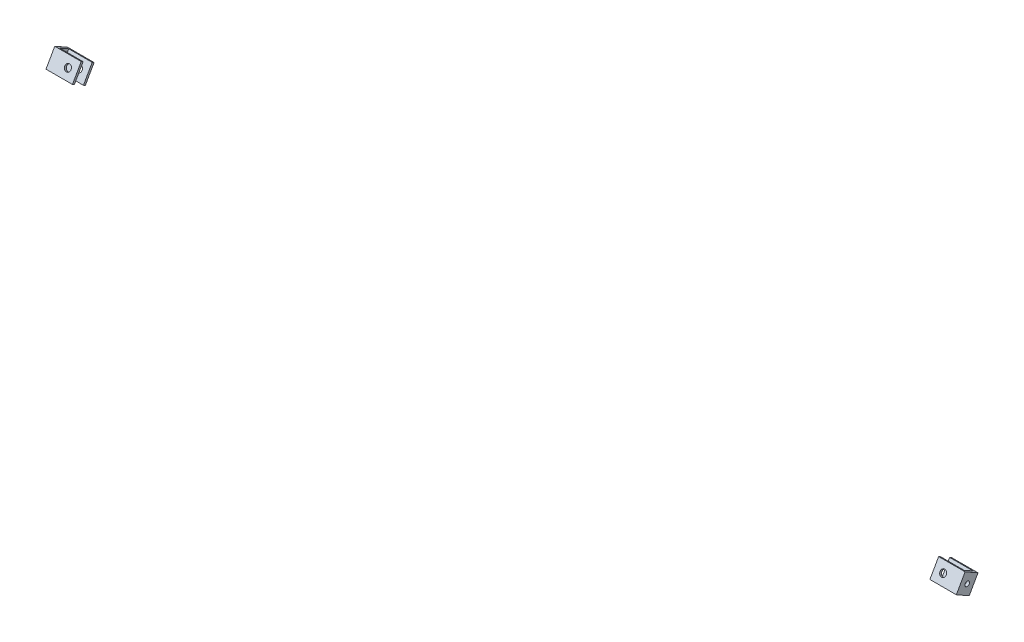
SolidWorks part; units mm, degrees
ref_plane "Front Plane" through (0, 0, 0) normal (0, 0, 1) x (1, 0, 0)
ref_plane "Top Plane" through (0, 0, 0) normal (0, 1, 0) x (1, 0, 0)
ref_plane "Right Plane" through (0, 0, 0) normal (1, 0, 0) x (0, 0, -1)
ref_plane "Plane1" through (0, -217.9452, -384.9482) normal (0, -0.4927, -0.8702) x (-1, 0, 0)
sketch "Sketch1" plane through (0, -217.9452, -384.9482) normal (0, -0.4927, -0.8702) x (-1, 0, 0)
  line L0 (487.45, 1279.1709) -> (468.654, 1279.1709) construction
  line L1 (487.45, 1279.1709) -> (468.654, 1279.1709) construction
  line L2 (487.45, 1288.6959) -> (487.45, 1269.6459)
  line L3 (487.45, 1427.6969) -> (487.45, 1247.6609) construction
  line L4 (487.45, 1288.6959) -> (459.129, 1288.6959)
  line L5 (459.129, 1288.6959) -> (459.129, 1269.6459)
  line L6 (459.129, 1269.6459) -> (487.45, 1269.6459)
  circle A0 centre (468.654, 1279.1709) radius 3.3782
  point P6 (487.45, 1279.1709)
  dimension "D1" = 6.7564
  dimension "D2" = 9.525
  dimension "D3" = 9.525
extrude "Boss-Extrude1" add sketch "Sketch1" along normal mid plane 15.875
sketch "Sketch2" plane through (0, 1104.8565, -625.534) normal (0, -0.8702, 0.4927) x (1, 0, 0)
  line L0 (-487.45, -442.3632) -> (-459.129, -442.3632) construction
  line L1 (-484.275, -436.807) -> (-452.4806, -436.807)
  line L2 (-484.275, -436.807) -> (-484.275, -447.9195)
  line L3 (-484.275, -447.9195) -> (-452.4806, -447.9195)
  line L4 (-452.4806, -436.807) -> (-452.4806, -447.9195)
  line L8 (-459.129, -434.4257) -> (-487.45, -434.4257)
  line L9 (-487.45, -434.4257) -> (-487.45, -450.3007)
  line L10 (-487.45, -450.3007) -> (-459.129, -450.3007)
  line L11 (-459.129, -450.3007) -> (-459.129, -434.4257)
  line L12 (-459.129, -434.4257) -> (-487.45, -434.4257) construction
  line L13 (-487.45, -434.4257) -> (-487.45, -450.3007) construction
  line L14 (-487.45, -450.3007) -> (-459.129, -450.3007) construction
  line L15 (-459.129, -450.3007) -> (-459.129, -434.4257) construction
  dimension "D1" = 11.1125
  dimension "D3" = 3.175
  dimension "D2" = 0
extrude "Cut-Extrude1" cut sketch "Sketch2" against normal through all
sketch "Sketch3" plane through (-487.45, 0, 0) normal (-1, 0, 0) x (0, 0, 1)
  line L0 (-1019.8678, 903.4887) -> (-1010.4822, 886.9113) construction
  line L1 (-1022.0823, 891.2893) -> (-1008.2677, 899.1107) construction
  line L4 (-1003.5749, 890.8219) -> (-1012.9605, 907.3994)
  line L5 (-1012.9605, 907.3994) -> (-1026.7751, 899.5781)
  line L6 (-1026.7751, 899.5781) -> (-1017.3895, 883.0006)
  line L7 (-1017.3895, 883.0006) -> (-1003.5749, 890.8219)
  line L8 (-1003.5749, 890.8219) -> (-1012.9605, 907.3994) construction
  line L9 (-1012.9605, 907.3994) -> (-1026.7751, 899.5781) construction
  line L10 (-1026.7751, 899.5781) -> (-1017.3895, 883.0006) construction
  line L11 (-1017.3895, 883.0006) -> (-1003.5749, 890.8219) construction
  circle A0 centre (-1015.175, 895.2) radius 2.5527
  dimension "D2" = 5.1054
  dimension "D1" = 0
extrude "Cut-Extrude2" cut sketch "Sketch3" against normal through all
mirror "Mirror2" about plane through (0, 0, 0) normal (1, 0, 0) of bodies 103
